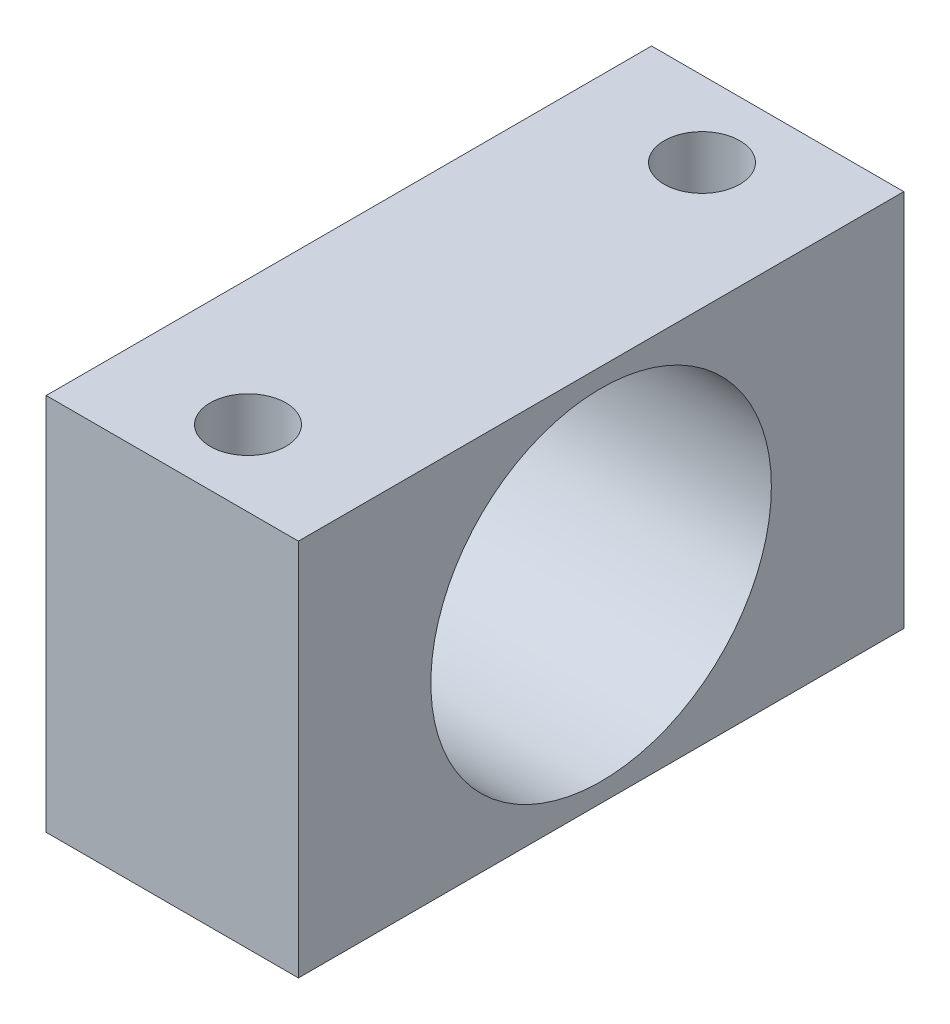
SolidWorks part; units mm, degrees
ref_plane "Front Plane" through (0, 0, 0) normal (0, 0, 1) x (1, 0, 0)
ref_plane "Top Plane" through (0, 0, 0) normal (0, 1, 0) x (1, 0, 0)
ref_plane "Right Plane" through (0, 0, 0) normal (1, 0, 0) x (0, 0, -1)
sketch "Sketch2" plane through (0, 0, 0) normal (0, 1, 0) x (1, 0, 0)
  line L0 (-5, 0) -> (5, 0) construction
  line L1 (-5, -12) -> (5, -12)
  line L2 (-5, -12) -> (-5, 12)
  line L3 (-5, 12) -> (5, 12)
  line L4 (5, -12) -> (5, 12)
  line L5 (-5, -12) -> (5, 12) construction
  line L6 (-5, 12) -> (5, -12) construction
  circle A0 centre (0, 9) radius 1.5
  circle A1 centre (0, -9) radius 1.5
  point P0 (0, 0)
  dimension "D3" = 3
  dimension "D1" = 10
  dimension "D2" = 24
  dimension "D4" = 9
extrude "Boss-Extrude1" add sketch "Sketch2" along normal blind 15
sketch "Sketch3" plane through (5, 0, 0) normal (1, 0, 0) x (0, 0, -1)
  line L0 (-12, 7.5) -> (12, 7.5) construction
  line L1 (-12, 15) -> (-12, 0) construction
  line L2 (12, 15) -> (12, 0) construction
  circle A0 centre (0, 7.5) radius 6.75
  dimension "D1" = 13.5
extrude "Cut-Extrude1" cut sketch "Sketch3" against normal up to surface (10 mm away) up to face at (-5, 7.5, 0)
